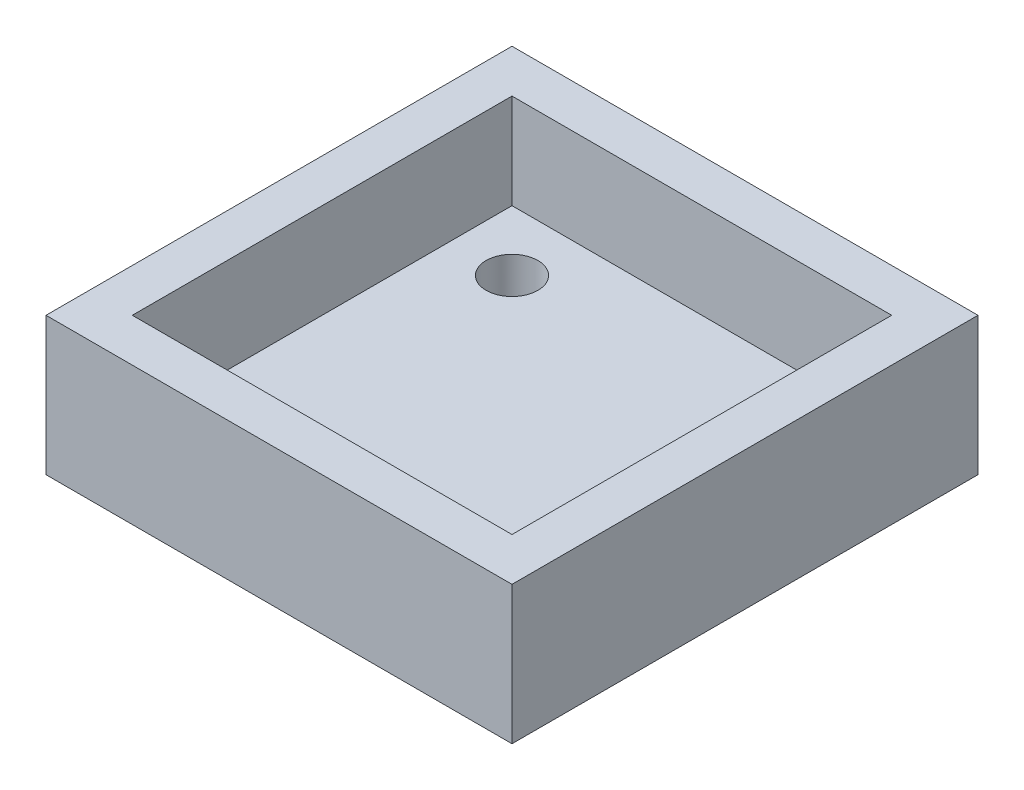
SolidWorks part; units mm, degrees
ref_plane "Front Plane" through (0, 0, 0) normal (0, 0, 1) x (1, 0, 0)
ref_plane "Top Plane" through (0, 0, 0) normal (0, 1, 0) x (1, 0, 0)
ref_plane "Right Plane" through (0, 0, 0) normal (1, 0, 0) x (0, 0, -1)
sketch "Sketch2" plane through (0, 0, 0) normal (0, 1, 0) x (1, 0, 0)
  line L1 (0, 0) -> (27, 0)
  line L2 (0, 0) -> (0, 27)
  line L3 (0, 27) -> (27, 27)
  line L4 (27, 0) -> (27, 27)
  dimension "D1" = 27
  dimension "D2" = 27
extrude "Boss-Extrude1" add sketch "Sketch2" along normal blind 8 contours L2 L1 L4 L3
sketch "Sketch5" plane through (0, 8, 0) normal (0, 1, 0) x (1, 0, 0)
  line L0 (0, 0) -> (27, 0) construction
  line L1 (27, 0) -> (27, 27) construction
  line L5 (2.5, 24.5) -> (24.5, 24.5)
  line L6 (2.5, 24.5) -> (2.5, 2.5)
  line L7 (2.5, 2.5) -> (24.5, 2.5)
  line L8 (24.5, 24.5) -> (24.5, 2.5)
  line L9 (2.5, 24.5) -> (24.5, 2.5) construction
  line L10 (2.5, 2.5) -> (24.5, 24.5) construction
  point P0 (13.5, 13.5)
  dimension "D1" = 22
  dimension "D2" = 22
  dimension "D3" = 2.5
  dimension "D4" = 2.5
extrude "Cut-Extrude2" cut sketch "Sketch5" against normal blind 5.5
sketch "Sketch3" plane through (0, 0, 0) normal (0, -1, 0) x (-1, 0, 0)
  line L3 (0, 27) -> (-27, 27) construction
  circle A1 centre (-6, 21) radius 1.5
  circle A2 centre (-6, 5) radius 1.5
  dimension "D1" = 3
  dimension "D2" = 3
  dimension "D5" = 16
  dimension "D7" = 6
  dimension "D8" = 6
extrude "Cut-Extrude3" cut sketch "Sketch3" against normal blind 10
sketch "Sketch6" plane through (0, 2.5, 0) normal (0, 1, 0) x (1, 0, 0)
  line L2 (19.5, 22.25) -> (19.5, 5.75)
  line L4 (24.5, 2.5) -> (24.5, 24.5)
  line L5 (24.5, 24.5) -> (2.5, 24.5)
  line L6 (2.5, 24.5) -> (2.5, 2.5)
  line L7 (2.5, 2.5) -> (24.5, 2.5)
  line L8 (24.5, 5.75) -> (24.5, 22.25)
  line L12 (24.5, 22.25) -> (24.5, 5.75)
  arc A0 (22.25, 3) -> (24.5, 5.75) centre (21.6944, 5.75) ccw
  arc A1 (24.5, 22.25) -> (22.25, 25) centre (21.6944, 22.25) ccw
  arc A2 (19.5, 5.75) -> (22.25, 3) centre (22.25, 5.75) ccw
  arc A3 (22.25, 25) -> (19.5, 22.25) centre (22.25, 22.25) ccw
  line M7 (24.5, 2.5) -> (24.5, 24.5)
  line M8 (24.5, 24.5) -> (2.5, 24.5)
  line M10 (2.5, 2.5) -> (24.5, 2.5)
  dimension "D2" = 0
  dimension "D1" = 0
extrude "Cut-Extrude4" cut sketch "Sketch6" against normal blind 10 contours L2 M8 M10 M7 region at (22.001, 2.5, -13.9091)
